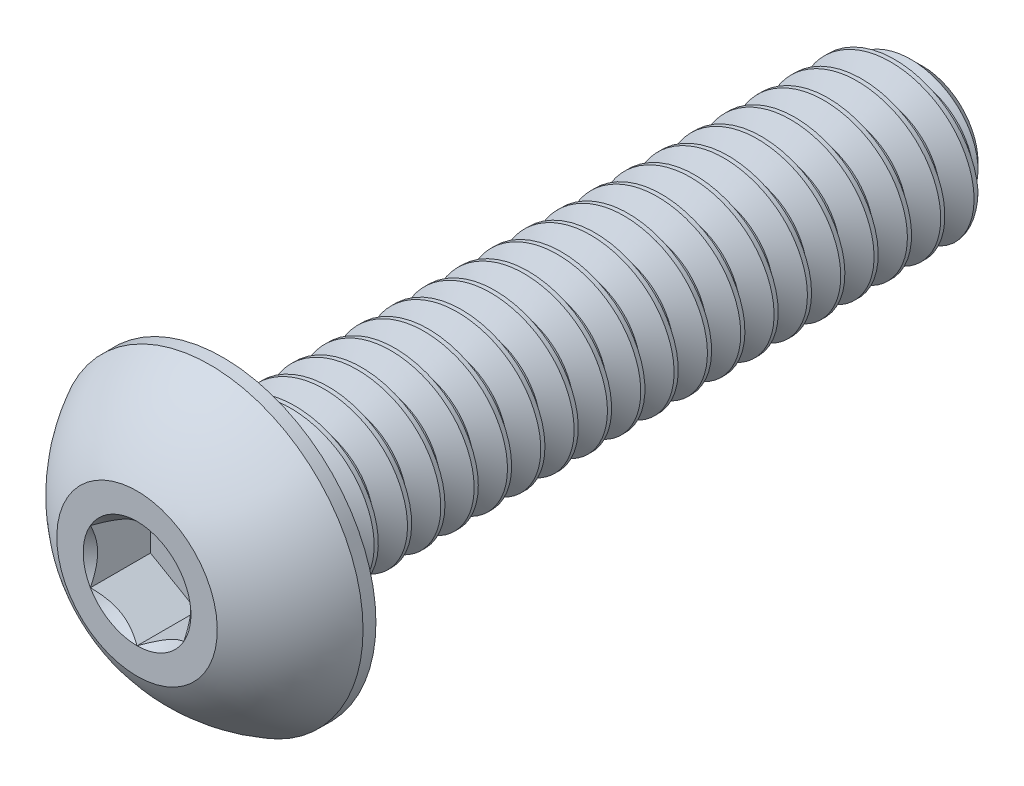
SolidWorks part; units mm, degrees
ref_plane "Front" through (0, 0, 0) normal (0, 0, 1) x (1, 0, 0)
ref_plane "Top" through (0, 0, 0) normal (0, 1, 0) x (1, 0, 0)
ref_plane "Right" through (0, 0, 0) normal (1, 0, 0) x (0, 0, -1)
sketch "Sketch1" plane through (0, 0, 0) normal (1, 0, 0) x (0, 0, -1)
  line L2 (1.1684, 1.0922) -> (10.6934, 1.0922)
  line L3 (10.6934, 1.0922) -> (10.6934, 0)
  line L4 (10.6934, 0) -> (1.1684, 0)
  line L6 (0.9931, 2.0828) -> (1.1684, 2.0828) construction
  line L7 (10.6934, 1.0922) -> (10.6934, -1.0922) construction
  line L8 (0, 0) -> (1.1684, 0) construction
  line L9 (1.1684, 2.0828) -> (1.1684, -2.0828) construction
  line L11 (1.1684, 1.0922) -> (1.1684, 0)
  line L13 (0, 0.635) -> (0, -0.635) construction
  line L14 (0, 0.635) -> (0, 1.0922) construction
  arc A3 (0, 1.0922) -> (0.9931, 2.0828) centre (2.08, 0) cw construction
  dimension "D1" = 0.1753
revolve "Revolve1" add sketch "Sketch1" angle 360 mid plane about L4
sketch "Sketch3" plane through (0, 0, -10.6934) normal (0, 0, -1) x (-1, 0, 0)
  circle A0 centre (0, 0) radius 1.0922
curve "Helix/Spiral1" pitch 0.4536 height 9.9786 radius 1.0922 centre (0, 0, -10.6934) axis (0, 0, 1) start towards (0, 1, 0)
sketch "Sketch2" plane through (0, 0, 0) normal (1, 0, 0) x (0, 0, -1)
  line L0 (10.6934, 1.0922) -> (11.0903, 1.0922)
  line L1 (11.0903, 1.0922) -> (10.9202, 0.7976)
  line L2 (10.9202, 0.7976) -> (10.8635, 0.7976)
  line L3 (10.8635, 0.7976) -> (10.6934, 1.0922)
  line L4 (10.7784, 0.9449) -> (11.0052, 0.9449) construction
  dimension "D1" = 60
  dimension "D2" = 0.0567
  dimension "D3" = 0.2268
chamfer "Chamfer1" distance 0.3402 angle 45 1 edges at (0, 1.0922, -10.6934)
sweep "Cut-Sweep1" cut profiles "Sketch2" path "Helix/Spiral1"
sketch "Sketch7" plane through (0, 0, 0) normal (1, 0, 0) x (0, 0, -1)
  line L6 (0.9931, 2.0828) -> (1.1684, 2.0828) construction
  line L8 (0, 0) -> (1.1684, 0) construction
  line L11 (1.1684, 2.0828) -> (1.1684, -2.0828) construction
  line L12 (0.9931, 2.0828) -> (1.1684, 2.0828)
  line L13 (0, 0) -> (1.1684, 0)
  line L14 (0, 0.635) -> (0, -0.635) construction
  line L15 (1.1684, 2.0828) -> (1.1684, 0)
  line L16 (0, 1.0922) -> (0, 0)
  arc A2 (0.9931, 2.0828) -> (0, 1.0922) centre (2.08, 0) ccw construction
  arc A3 (0.9931, 2.0828) -> (0, 1.0922) centre (2.08, 0) ccw
revolve "Revolve2" add sketch "Sketch7" angle 360 mid plane about L13
sketch "Sketch5" plane through (0, 0, 0) normal (0, 0, 1) x (1, 0, 0)
  line L1 (0.635, -0.3666) -> (0.635, 0.3666)
  line L2 (0.635, 0.3666) -> (0, 0.7332)
  line L3 (0, 0.7332) -> (-0.635, 0.3666)
  line L4 (-0.635, 0.3666) -> (-0.635, -0.3666)
  line L5 (-0.635, -0.3666) -> (0, -0.7332)
  line L6 (0, -0.7332) -> (0.635, -0.3666)
  circle A0 centre (0, 0) radius 0.635 construction
extrude "Cut-Extrude2" cut sketch "Sketch5" against normal blind 0.8179
sketch "Sketch6" plane through (0, 0, 0) normal (0, 0, 1) x (1, 0, 0)
  circle A0 centre (0, 0) radius 0.7332
extrude "Cut-Extrude3" cut sketch "Sketch6" against normal blind 0.8179 draft 45
sketch "Sketch9" [suppressed] plane through (0, 0, -5.0546) normal (0, 0, 1) x (1, 0, 0)
  circle A2 centre (0, 0) radius 4.7625
extrude "Boss-Extrude2" [suppressed] add sketch "Sketch9" against normal offset from surface (12.7 mm away) 31.75 up to face at (0, 0.752, -10.6934)
sketch "Sketch10" plane through (0, 0, 0) normal (1, 0, 0) x (0, 0, -1)
  line L0 (10.6934, 1.0922) -> (10.6934, -1.0922) construction
  point P0 (10.013, -1.0922)
  dimension "D1" = 0.6804
equation "\"D3@Helix/Spiral1\" = \"Lg@Sketch1\" + \"D4@Helix/Spiral1\""
equation "\"D2@Sketch2\" = \"D4@Helix/Spiral1\" * .125"
equation "\"D3@Sketch2\" = \"D4@Helix/Spiral1\" * .5"
equation "\"D1@Chamfer1\" = \"D4@Helix/Spiral1\" * .75"
equation "\"D1@Cut-Extrude2\" = \"Head Ht@Sketch1\" * .7"
equation "\"D1@Sketch1\" = \"Head Ht@Sketch1\" * .15"
equation "\"D1@Sketch10\" = \"D4@Helix/Spiral1\" * 1.5"
equation "\"D1@Cut-Extrude3\" = \"D1@Cut-Extrude2\""
